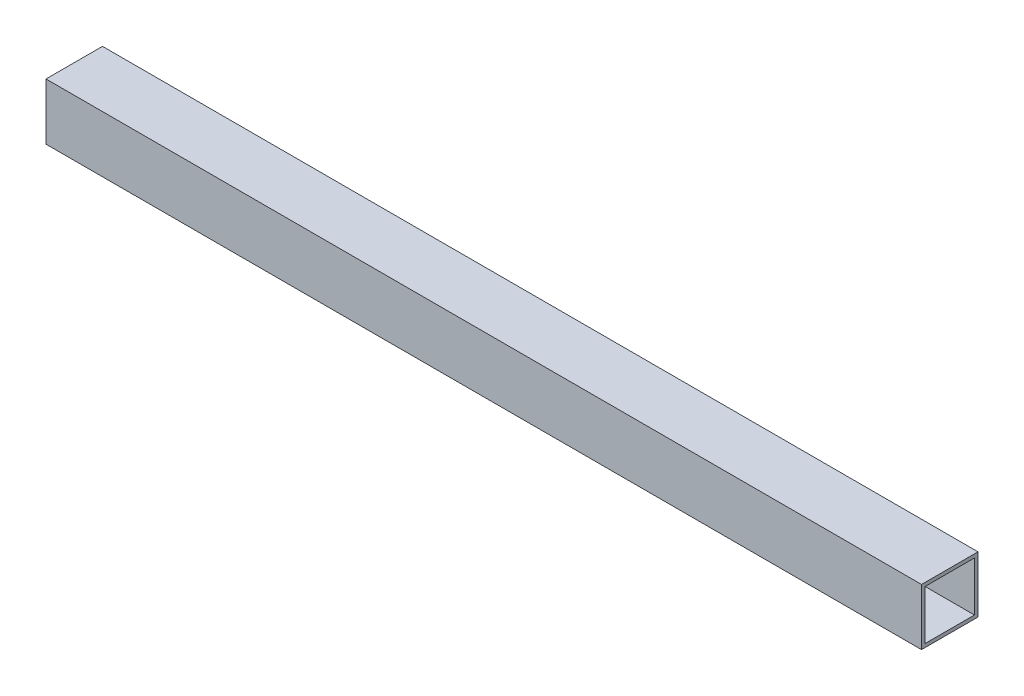
SolidWorks part; units mm, degrees
material "6061-T6 (SS)"
ref_plane "Front" through (0, 0, 0) normal (0, 0, 1) x (1, 0, 0)
ref_plane "Top" through (0, 0, 0) normal (0, 1, 0) x (1, 0, 0)
ref_plane "Right" through (0, 0, 0) normal (1, 0, 0) x (0, 0, -1)
sketch "Sketch1" plane through (0, 0, 0) normal (1, 0, 0) x (0, 0, -1)
  line L1 (-12.7, -12.7) -> (12.7, -12.7)
  line L2 (-12.7, -12.7) -> (-12.7, 12.7)
  line L3 (-12.7, 12.7) -> (12.7, 12.7)
  line L4 (12.7, -12.7) -> (12.7, 12.7)
  line L5 (-12.7, -12.7) -> (12.7, 12.7) construction
  line L6 (-12.7, 12.7) -> (12.7, -12.7) construction
  point P0 (0, 0)
  dimension "D1" = 25.4
extrude "Extrude-Thin1" add sketch "Sketch1" along normal up to surface (393.7 mm away) thin thin type one direction reverse wall 1.5875
